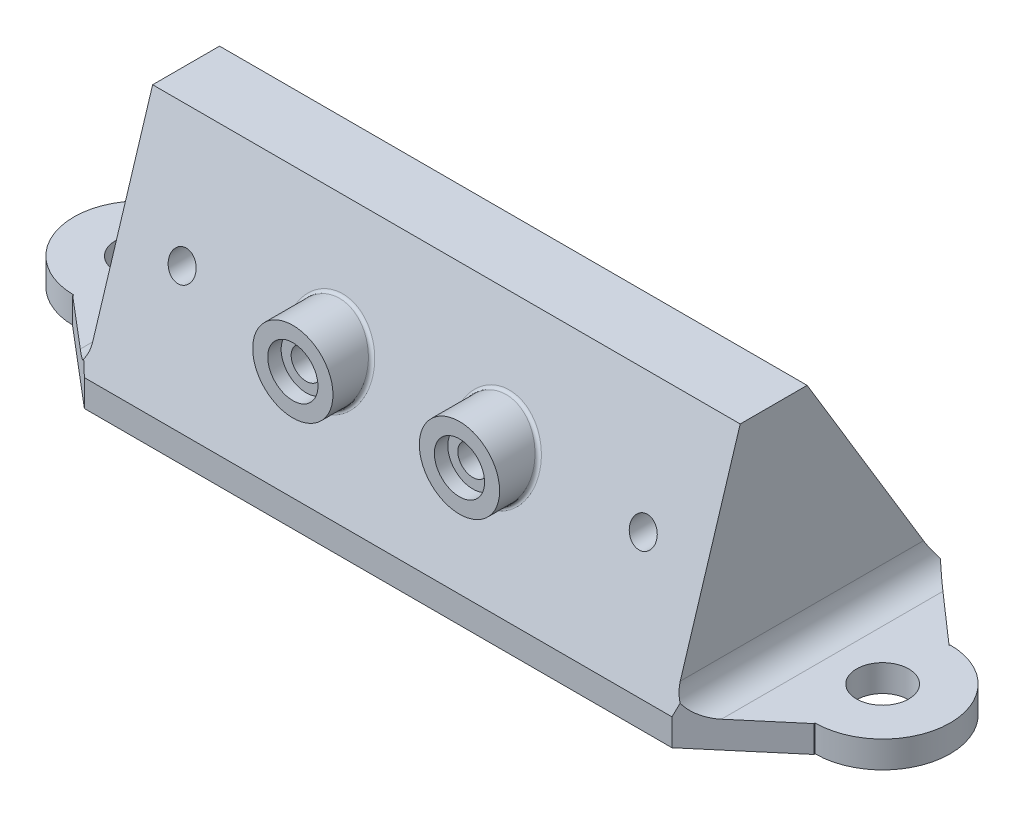
SolidWorks part; units mm, degrees
ref_plane "Front Plane" through (0, 0, 0) normal (0, 0, 1) x (1, 0, 0)
ref_plane "Top Plane" through (0, 0, 0) normal (0, 1, 0) x (1, 0, 0)
ref_plane "Right Plane" through (0, 0, 0) normal (1, 0, 0) x (0, 0, -1)
sketch "Sketch1" plane through (0, 0, 0) normal (0, 0, 1) x (1, 0, 0)
  line L1 (-39.9, -16.4) -> (39.9, -16.4)
  line L2 (-39.9, -16.4) -> (-39.9, 16.4)
  line L3 (-39.9, 16.4) -> (39.9, 16.4)
  line L4 (39.9, -16.4) -> (39.9, 16.4)
  line L5 (-39.9, -16.4) -> (39.9, 16.4) construction
  line L6 (-39.9, 16.4) -> (39.9, -16.4) construction
  point P0 (0, 0)
  dimension "D1" = 79.8
  dimension "D2" = 32.8
extrude "Boss-Extrude1" add sketch "Sketch1" along normal blind 10
sketch "Sketch3" plane through (0, -16.4, 0) normal (0, -1, 0) x (1, 0, 0)
  line L0 (39.9, 10) -> (39.9, 0) construction
  line L1 (-39.9, 0) -> (39.9, 0)
  line L2 (-39.9, 0) -> (-39.9, 20.2)
  line L3 (-39.9, 20.2) -> (39.9, 20.2)
  line L4 (39.9, 0) -> (39.9, 20.2)
  line L6 (-39.9, 0) -> (39.9, 0)
  line L7 (-39.9, 0) -> (-39.9, -19.8)
  line L8 (-39.9, -19.8) -> (39.9, -19.8)
  line L9 (39.9, 0) -> (39.9, -19.8)
  line M3 (-39.9, 0) -> (39.9, 0)
  line M4 (39.9, 0) -> (39.9, 10)
  line M5 (39.9, 10) -> (-39.9, 10)
  line M6 (-39.9, 10) -> (-39.9, 0)
  dimension "D1" = 19.8
  dimension "D2" = 40
extrude "Boss-Extrude3" add sketch "Sketch3" along normal blind 4 contours L9 L7 L8 M3 | L4 L3 L2 M5 | M6 M3 M4 M5 region at (0, -16.4, 5) region at (0, -16.4, -9.9) region at (0, -16.4, 15.1)
sketch "Sketch4" plane through (-39.9, 0, 0) normal (-1, 0, 0) x (0, 0, 1)
  line L0 (10, 16.4) -> (20.2, -16.4)
  line L1 (20.2, -16.4) -> (20.2, -20.4)
  line L2 (20.2, -20.4) -> (-19.8, -20.4)
  line L3 (-19.8, -20.4) -> (-19.8, -16.4)
  line L4 (-19.8, -16.4) -> (0, 16.4)
  line L5 (10, 16.4) -> (0, 16.4) construction
  line L6 (0, 16.4) -> (10, 16.4)
extrude "Boss-Extrude4" add sketch "Sketch4" along normal blind 4
mirror "Mirror1" about plane through (0, 0, 0) normal (1, 0, 0) of "Boss-Extrude4"
sketch "Sketch5" plane through (0, -20.4, 0) normal (0, -1, 0) x (1, 0, 0)
  line L0 (43.9, 0.2) -> (11.1313, 0.2) construction
  line L2 (43.9, 20.2) -> (43.9, -19.8)
  line L5 (43.9, -19.8) -> (43.9, 20.2) construction
  line L15 (55.3867, -9.8927) -> (55.3867, -9.7266)
  line L16 (55.3867, -9.7266) -> (43.9, -19.8)
  line L17 (55.3867, 10.2927) -> (55.3867, 10.4587)
  line L18 (55.3867, 10.4587) -> (43.9, 20.2)
  circle A0 centre (55.3867, 0.2) radius 3.9
  arc A1 (55.3867, -9.8927) -> (55.3867, 10.2927) centre (55.3867, 0.2) ccw
  dimension "D1" = 32.7687
  dimension "D2" = 7.8
extrude "Boss-Extrude5" add sketch "Sketch5" against normal blind 4
mirror "Mirror2" about plane through (0, 0, 0) normal (1, 0, 0) of "Boss-Extrude5"
fillet "Fillet3" radius 4 2 edges at (43.9, -16.4, 0.2) (-43.9, -16.4, 0.2)
fillet "Fillet4" radius 1 1 edges at (0, -16.4, 0)
sketch "Sketch11" plane through (-39.9, 0, 0) normal (1, 0, 0) x (0, 0, -1)
  line L0 (-20.2, -16.4) -> (-10, -16.4)
  line L1 (-10, -16.4) -> (-10, 16.4)
  line L2 (-10, 16.4) -> (-20.2, -16.4)
extrude "Boss-Extrude9" add sketch "Sketch11" along normal up to surface (79.8 mm away) up to face at (39.9, -5.4667, 13.4)
sketch "Sketch6" plane through (0, 0, 0) normal (0, 0, -1) x (-1, 0, 0)
  line L0 (0, 23.3624) -> (0, -33.4379) construction
  line L1 (-10.2, 0.25) -> (0, 0.25) construction
  line L2 (-12.45, 2.5) -> (-12.45, 16.4) construction
  line L3 (-39.9, 16.4) -> (39.9, 16.4) construction
  line L4 (32.45, 0.2) -> (0, 0.2) construction
  line L5 (34.45, 2.2) -> (34.45, 16.4) construction
  circle A0 centre (-12.45, 0.25) radius 2.25
  circle A1 centre (12.45, 0.25) radius 2.25
  circle A2 centre (34.45, 0.2) radius 2
  circle A3 centre (-34.45, 0.2) radius 2
  dimension "D3" = 4.5
  dimension "D4" = 4
  dimension "D1" = 10.2
  dimension "D2" = 13.9
  dimension "D5" = 14.2
  dimension "D6" = 32.45
extrude "Cut-Extrude1" cut sketch "Sketch6" against normal blind 38.2
ref_plane "Plane1" through (0, 0, 18.5) normal (0, 0, -1) x (-1, 0, 0)
sketch "Sketch12" plane through (0, 0, 18.5) normal (0, 0, -1) x (-1, 0, 0)
  circle A0 centre (-12.45, 0.25) radius 2.25 construction
  circle A1 centre (12.45, 0.25) radius 2.25 construction
  circle A2 centre (-12.45, 0.25) radius 2.25
  circle A3 centre (12.45, 0.25) radius 2.25
  circle A4 centre (12.45, 0.25) radius 6
  circle A5 centre (-12.45, 0.25) radius 6
  dimension "D1" = 12
  dimension "D2" = 12
extrude "Boss-Extrude10" add sketch "Sketch12" along normal up to surface (3.4777 mm away) up to face at (34.45, 2.2, 14.4159)
sketch "Sketch14" plane through (0, 0, 18.5) normal (0, 0, 1) x (1, 0, 0)
  circle A0 centre (-12.45, 0.25) radius 3.75
  circle A1 centre (12.45, 0.25) radius 3.75
  circle A2 centre (-12.45, 0.25) radius 6 construction
  circle A3 centre (12.45, 0.25) radius 6 construction
  circle A4 centre (-12.45, 0.25) radius 6
  circle A9 centre (12.45, 0.25) radius 6
  dimension "D1" = 7.5
  dimension "D2" = 7.5
extrude "Boss-Extrude11" add sketch "Sketch14" along normal blind 2
fillet "Fillet5" radius 0.5 2 edges at (12.45, -5.75, 16.8881) (-12.45, -5.75, 16.8881)
